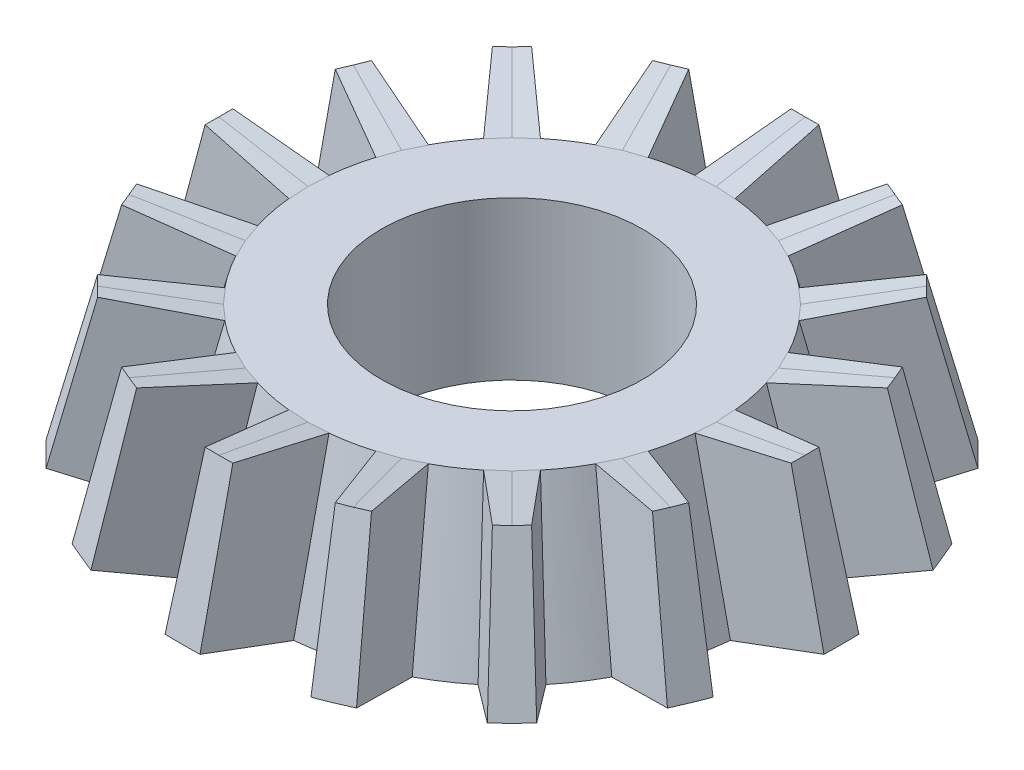
SolidWorks part; units mm, degrees
material "ABS"
ref_plane "Front Plane" through (0, 0, 0) normal (0, 0, 1) x (1, 0, 0)
ref_plane "Top Plane" through (0, 0, 0) normal (0, 1, 0) x (1, 0, 0)
ref_plane "Right Plane" through (0, 0, 0) normal (1, 0, 0) x (0, 0, -1)
sketch "Sketch1" plane through (0, 0, 0) normal (0, 0, 1) x (1, 0, 0)
  line L0 (0, 0) -> (10.264, 0)
  line L1 (10.264, 0) -> (8.5998, 6.6551)
  line L2 (8.5998, 6.6551) -> (0, 6.6551)
  line L3 (0, 6.6551) -> (0, 0)
  dimension "D1" = 10.264
  dimension "D2" = 75.96
  dimension "D3" = 6.86
revolve "Revolve1" add sketch "Sketch1" angle 360 about L3
sketch "Sketch2" plane through (0, 0, 0) normal (0, 0, 1) x (1, 0, 0)
  line L0 (0, 0) -> (0, 67.611) construction
  line L1 (0, 67.611) -> (0, -92.6067) construction
sketch "Sketch3" plane through (0, 0, 0) normal (1, 0, 0) x (0, 0, -1)
  line L0 (-10.264, 0) -> (-8.5998, 6.6551) construction
  line L1 (-8.5998, 6.6551) -> (0, 41.0446) construction
  line L2 (0, 67.611) -> (0, -92.6067) construction
  line L3 (0, 41.0446) -> (-39.1729, -115.6035) construction
ref_plane "Plane1" through (0, 2.4157, 9.6599) normal (0, 0.2426, 0.9701) x (1, 0, 0)
sketch "Sketch8" plane through (0, 2.4157, 9.6599) normal (0, 0.2426, 0.9701) x (1, 0, 0)
  line L0 (0, 4.37) -> (0.8443, 4.38)
  line L1 (0.8443, 4.38) -> (1.0077, -2.478)
  line L2 (1.0077, -2.478) -> (0, -2.49)
  line L3 (0, -2.49) -> (-1.0077, -2.478)
  line L4 (-1.0077, -2.478) -> (-0.8443, 4.38)
  line L5 (-0.8443, 4.38) -> (0, 4.37)
  ellipse E0 centre (0, 6.4563) end of major axis (8.5998, 6.4563) minor radius 2.0863 construction
  ellipse E1 centre (0, 0) end of major axis (10.264, 0) minor radius 2.49 construction
  dimension "D1" = 1.0077
  dimension "D2" = 1.0077
  dimension "D3" = 0.8443
  dimension "D4" = 0.8443
extrude "Boss-Extrude1" add sketch "Sketch8" along normal blind 3.8 draft 4 and the other way blind 0.1 draft 4 other way draft outward yes
pattern_circular "CirPattern5" count 16 over 360 about axis through (0, 67.611, 0) along (0, -1, 0) of "Boss-Extrude1"
sketch "Sketch9" plane through (0, 6.6551, 0) normal (0, 1, 0) x (1, 0, 0)
  circle A0 centre (0, 0) radius 5.5
  dimension "D1" = 11
extrude "Cut-Extrude1" cut sketch "Sketch9" against normal blind 11.5
sketch "Sketch11" plane through (0, 0, 0) normal (0, -1, 0) x (1, 0, 0)
  circle A0 centre (0, 0) radius 13.97
extrude "Cut-Extrude4" cut sketch "Sketch11" along normal blind 10
